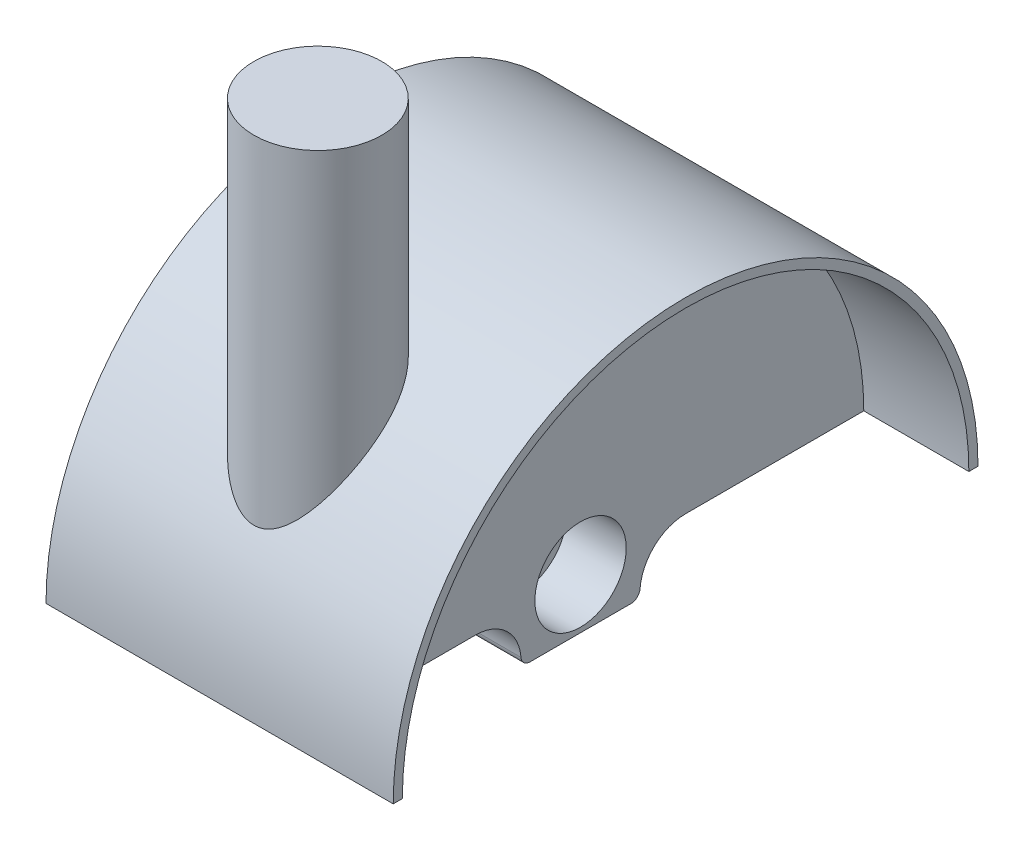
SolidWorks part; units mm, degrees
ref_plane "Front Plane" through (0, 0, 0) normal (0, 0, 1) x (1, 0, 0)
ref_plane "Top Plane" through (0, 0, 0) normal (0, 1, 0) x (1, 0, 0)
ref_plane "Right Plane" through (0, 0, 0) normal (1, 0, 0) x (0, 0, -1)
sketch "Sketch1" plane through (0, 0, 0) normal (1, 0, 0) x (0, 0, -1)
  line L0 (-32, 0) -> (32, 0)
  line L2 (-31, 0) -> (31, 0) construction
  line L3 (-31.9844, -1) -> (31.9844, -1) construction
  arc A0 (31, 0) -> (-31, 0) centre (0, 0) ccw
  arc A1 (32, 0) -> (-32, 0) centre (0, 0) ccw
  arc A2 (31.9844, -1) -> (-31.9844, -1) centre (0, 0) ccw construction
  point P6 (0, 0)
  dimension "D1" = 62
  dimension "D2" = 1
extrude "Boss-Extrude1" add sketch "Sketch1" along normal blind 19 contours L0 A1 A0 region at (0, 31.2845, 0)
extrude "Boss-Extrude2" add sketch "Sketch1<3>" along normal blind 7.5 contours L0 A0 region at (0, 13.1568, 0)
sketch "Sketch1<3>" plane through (0, 0, 0) normal (1, 0, 0) x (0, 0, -1) same geometry as "Sketch1"
sketch "Sketch2" plane through (7.5, 0, 0) normal (1, 0, 0) x (0, 0, -1)
  line L0 (-31, 0) -> (31, 0) construction
  line L2 (-6.5, 0) -> (6.5, 0)
  line L3 (-6.5, 0) -> (-6.5, -5.5293)
  line L4 (-6.5, -5.5293) -> (6.5, -5.5293)
  line L5 (6.5, 0) -> (6.5, -5.5293)
  circle A0 centre (0, 0) radius 5
  point P8 (0, 0)
  line M6 (-31, 0) -> (31, 0)
  dimension "D1" = 10
  dimension "D2" = 13
extrude "Boss-Extrude3" add sketch "Sketch2" against normal blind 7.5 contours A0 L3 L4 L5 M6 | L2 A0 region at (7.5, -2.1221, 0) region at (7.5, -0.1413, -5.75)
extrude "Cut-Extrude1" cut sketch "Sketch2<3>" against normal blind 6.5 contours L2 A0 | L2 A0 region at (7.5, -2.1221, 0) region at (7.5, 2.1221, 0)
sketch "Sketch2<3>" plane through (7.5, 0, 0) normal (1, 0, 0) x (0, 0, -1) same geometry as "Sketch2"
mirror "Mirror2" about plane through (0, 0, 0) normal (1, 0, 0) of bodies 105
fillet "Fillet2" radius 5 1 edges at (0, 0, -6.5) type face fillet first side face at (0, -2.7646, -6.5) second side face at (0, 0, -25.125)
fillet "Fillet3" radius 5 1 edges at (0, 0, 6.5) type face fillet first side face at (0, -2.7646, 6.5) second side face at (0, 0, 25.125)
fillet "Fillet4" radius 1 2 edges at (0, -5.5293, 6.5) (0, -5.5293, -6.5)
ref_plane "Plane1" through (0, 32, 0) normal (0, 1, 0) x (1, 0, 0)
sketch "Sketch3" plane through (0, 32, 0) normal (0, 1, 0) x (1, 0, 0)
  line L0 (-7.5, -11.5) -> (-7.5, -31) construction
  line L1 (-7.5, -21.25) -> (7.5, -21.25) construction
  line L2 (7.5, -31) -> (7.5, 31) construction
  circle A0 centre (0, -21.25) radius 7
  dimension "D1" = 14
extrude "Boss-Extrude4" add sketch "Sketch3" along normal blind 20 and the other way blind 18
